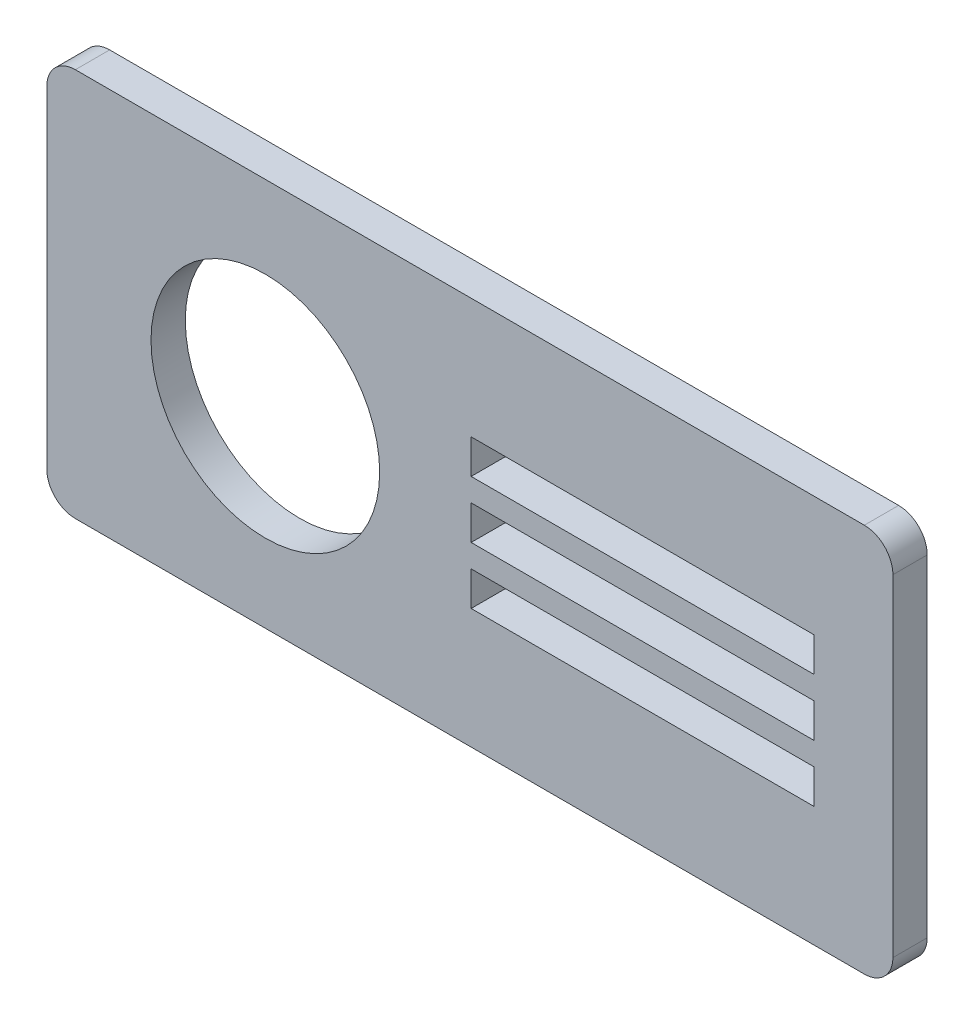
SolidWorks part; units mm, degrees
ref_plane "Front Plane" through (0, 0, 0) normal (0, 0, 1) x (1, 0, 0)
ref_plane "Top Plane" through (0, 0, 0) normal (0, 1, 0) x (1, 0, 0)
ref_plane "Right Plane" through (0, 0, 0) normal (1, 0, 0) x (0, 0, -1)
sketch "Sketch1" plane through (0, 0, 0) normal (0, 0, 1) x (1, 0, 0)
  line L0 (-78.5, 101.2037) -> (-147.5, 101.2037) construction
  line L1 (-75.5, 69.2037) -> (-75.5, 98.2037) construction
  line L2 (-147.5, 66.2037) -> (-78.5, 66.2037) construction
  line L3 (-150.5, 98.2037) -> (-150.5, 69.2037) construction
  line L4 (-78.5, 101.2037) -> (-147.5, 101.2037) construction
  line L5 (-75.5, 69.2037) -> (-75.5, 98.2037) construction
  line L6 (-147.5, 66.2037) -> (-78.5, 66.2037) construction
  line L7 (-150.5, 98.2037) -> (-150.5, 69.2037) construction
  line L8 (-130.8892, 83.5278) -> (-130.8863, 83.5278) construction
  line L9 (-150.5, 83.7037) -> (-75.5, 83.7037) construction
  line L10 (-150, 98.2037) -> (-150, 69.2037)
  line L11 (-112.8863, 85.2037) -> (-82.8863, 85.2037)
  line L12 (-112.8863, 85.2037) -> (-112.8863, 82.2037)
  line L13 (-112.8863, 82.2037) -> (-82.8863, 82.2037)
  line L14 (-82.8863, 85.2037) -> (-82.8863, 82.2037)
  line L15 (-112.8863, 87.2037) -> (-82.8863, 87.2037)
  line L16 (-112.8863, 87.2037) -> (-112.8863, 90.2037)
  line L17 (-112.8863, 90.2037) -> (-82.8863, 90.2037)
  line L18 (-82.8863, 87.2037) -> (-82.8863, 90.2037)
  line L19 (-112.8863, 80.2037) -> (-82.8863, 80.2037)
  line L20 (-112.8863, 80.2037) -> (-112.8863, 77.2037)
  line L21 (-112.8863, 77.2037) -> (-82.8863, 77.2037)
  line L22 (-82.8863, 80.2037) -> (-82.8863, 77.2037)
  line L23 (-147.5, 66.7037) -> (-78.5, 66.7037)
  line L24 (-76, 69.2037) -> (-76, 98.2037)
  line L25 (-78.5, 100.7037) -> (-147.5, 100.7037)
  arc A0 (-75.5, 98.2037) -> (-78.5, 101.2037) centre (-78.5, 98.2037) ccw construction
  arc A1 (-78.5, 66.2037) -> (-75.5, 69.2037) centre (-78.5, 69.2037) ccw construction
  arc A2 (-150.5, 69.2037) -> (-147.5, 66.2037) centre (-147.5, 69.2037) ccw construction
  arc A3 (-147.5, 101.2037) -> (-150.5, 98.2037) centre (-147.5, 98.2037) ccw construction
  arc A4 (-75.5, 98.2037) -> (-78.5, 101.2037) centre (-78.5, 98.2037) ccw construction
  arc A5 (-78.5, 66.2037) -> (-75.5, 69.2037) centre (-78.5, 69.2037) ccw construction
  arc A6 (-150.5, 69.2037) -> (-147.5, 66.2037) centre (-147.5, 69.2037) ccw construction
  arc A7 (-147.5, 101.2037) -> (-150.5, 98.2037) centre (-147.5, 98.2037) ccw construction
  circle A8 centre (-130.8863, 83.5278) radius 10
  arc A9 (-147.5, 100.7037) -> (-150, 98.2037) centre (-147.5, 98.2037) ccw
  arc A10 (-150, 69.2037) -> (-147.5, 66.7037) centre (-147.5, 69.2037) ccw
  arc A11 (-78.5, 66.7037) -> (-76, 69.2037) centre (-78.5, 69.2037) ccw
  arc A12 (-76, 98.2037) -> (-78.5, 100.7037) centre (-78.5, 98.2037) ccw
  dimension "D1" = 18
  dimension "D2" = 30
  dimension "D3" = 3
  dimension "D4" = 1.5
  dimension "D5" = 3
  dimension "D6" = 3
  dimension "D7" = 2
  dimension "D8" = 2
  dimension "D9" = 0.5
extrude "Boss-Extrude1" add sketch "Sketch1" against normal blind 3
